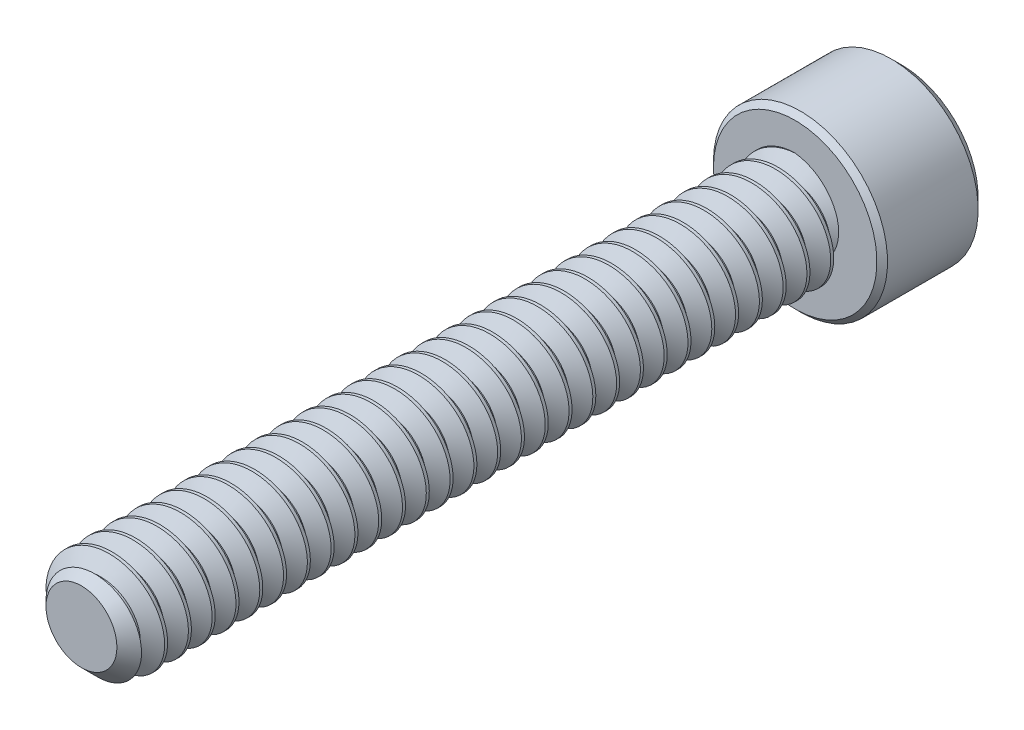
SolidWorks part; units mm, degrees
ref_plane "Front Plane" through (0, 0, 0) normal (0, 0, 1) x (1, 0, 0)
ref_plane "Top Plane" through (0, 0, 0) normal (0, 1, 0) x (1, 0, 0)
ref_plane "Right Plane" through (0, 0, 0) normal (1, 0, 0) x (0, 0, -1)
sketch "Sketch1" plane through (0, 0, 0) normal (0, 0, 1) x (1, 0, 0)
  line L0 (0, 1.4224) -> (0, -1.4224) construction
  circle A0 centre (0, 0) radius 1.4224
  dimension "OD" = 2.8448
extrude "Extrude1" add sketch "Sketch1" against normal blind 19.05
sketch "Sketch2" plane through (0, 0, 0) normal (0, 0, 1) x (1, 0, 0)
  circle A0 centre (0, 0) radius 1.4224 construction
  circle A1 centre (0, 0) radius 1.4224
curve "Helix/Spiral1" pitch 0.635 height 19.685 turns 31 parameters "pitch"=0.635
chamfer "Chamfer3" distance 0.4763 angle 45 1 edges at (1.4224, 0, 0)
sketch "Sketch3" plane through (0, 0, 0) normal (1, 0, 0) x (0, 0, -1)
  line L0 (-0.5556, 1.4224) -> (-0.3175, 1.01)
  line L1 (-0.3175, 1.01) -> (-0.2381, 1.01)
  line L2 (-0.2381, 1.01) -> (0, 1.4224)
  line L3 (-0.5556, 1.4224) -> (0, 1.4224)
  line L4 (-0.2778, 1.4224) -> (-0.2778, 1.01) construction
  line L5 (-0.4366, 1.2162) -> (-0.1191, 1.2162) construction
  line L6 (0, 1.4224) -> (0, -1.4224) construction
  dimension "D1" = 0.0794
  dimension "D2" = 0.3175
  dimension "D3" = 60
sweep "Cut-Sweep1" cut profiles "Sketch3" path "Helix/Spiral1"
sketch "Sketch6" plane through (0, 0, -19.05) normal (0, 0, -1) x (-1, 0, 0)
  circle A0 centre (0, 0) radius 2.3241
  dimension "head dia" = 4.6482
extrude "Extrude2" add sketch "Sketch6" along normal blind 2.8448
sketch "Sketch7" plane through (0, 0, -21.8948) normal (0, 0, -1) x (-1, 0, 0)
  line L1 (0, 1.3748) -> (-1.1906, 0.6874)
  line L2 (-1.1906, 0.6874) -> (-1.1906, -0.6874)
  line L3 (-1.1906, -0.6874) -> (0, -1.3748)
  line L4 (0, -1.3748) -> (1.1906, -0.6874)
  line L5 (1.1906, -0.6874) -> (1.1906, 0.6874)
  line L6 (1.1906, 0.6874) -> (0, 1.3748)
  circle A0 centre (0, 0) radius 1.1906 construction
  dimension "hex dia" = 2.3813
extrude "Cut-Extrude1" cut sketch "Sketch7" against normal blind 1.7859
sketch "Sketch8" plane through (0, 0, -21.8948) normal (0, 0, -1) x (-1, 0, 0)
  circle A0 centre (0, 0) radius 1.3748
extrude "Cut-Extrude2" cut sketch "Sketch8" against normal blind 0.2845 draft 45
chamfer "Chamfer1" distance 0.2845 angle 45 1 edges at (-2.3241, 0, -21.8948)
chamfer "Chamfer2" distance 0.1422 angle 45 1 edges at (-2.3241, 0, -19.05)
sketch "Sketch9" plane through (0, 0, 0) normal (1, 0, 0) x (0, 0, -1)
  line L0 (0, 1.4224) -> (0, -1.4224) construction
  line L1 (3.4925, 1.4224) -> (3.4925, -1.4224) construction
  line L2 (19.05, 2.3241) -> (19.05, -2.3241) construction
  line L3 (21.8948, 2.3241) -> (21.8948, -2.3241) construction
  line L4 (21.8948, 0) -> (0, 0) construction
  dimension "D1" = 3.4925
  dimension "D2" = 2.8448
  dimension "D3" = 4.6482
  dimension "D4" = 19.05
equation "\"D3@Helix/Spiral1\" = \"screw length@Extrude1\"+\"pitch@Helix/Spiral1\""
equation "\"D1@Sketch3\" = \"pitch@Helix/Spiral1\"*.125"
equation "\"D2@Sketch3\" = \"pitch@Helix/Spiral1\"*.5"
equation "\"D1@Cut-Extrude1\" = \"hex dia@Sketch7\"*.75"
equation "\"D1@Chamfer1\" = \"head depth@Extrude2\"/10"
equation "\"D1@Sketch9\" = \"pitch@Helix/Spiral1\"*5.5"
equation "\"D1@Chamfer2\" = \"D1@Chamfer1\"/2"
equation "\"D1@Cut-Extrude2\" = \"D1@Chamfer2\"*2"
equation "\"D1@Chamfer3\" = \"pitch@Helix/Spiral1\"*.750"
equation "\"D2@Sketch9\" = \"head depth@Extrude2\""
equation "\"D3@Sketch9\" = \"head dia@Sketch6\""
equation "\"D4@Sketch9\" = \"screw length@Extrude1\""
